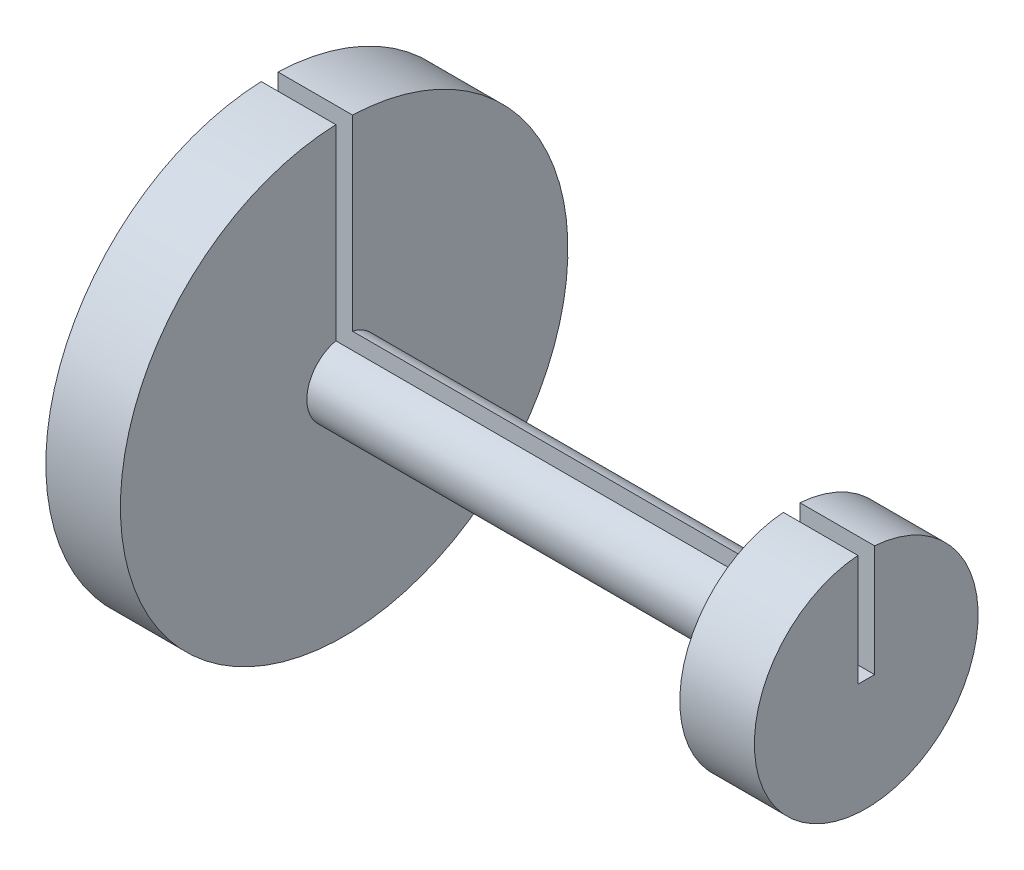
SolidWorks part; units mm, degrees
ref_plane "Front Plane" through (0, 0, 0) normal (0, 0, 1) x (1, 0, 0)
ref_plane "Top Plane" through (0, 0, 0) normal (0, 1, 0) x (1, 0, 0)
ref_plane "Right Plane" through (0, 0, 0) normal (1, 0, 0) x (0, 0, -1)
sketch "Sketch1" plane through (0, 0, 0) normal (0, 0, 1) x (1, 0, 0)
  line L0 (0, 0) -> (0, 30)
  line L1 (0, 30) -> (10, 30)
  line L2 (10, 30) -> (10, 5)
  line L3 (10, 5) -> (70, 5)
  line L4 (70, 5) -> (70, 15)
  line L5 (70, 15) -> (80, 15)
  line L6 (80, 15) -> (80, 0)
  line L7 (80, 0) -> (0, 0) construction
  line L8 (0, 0) -> (80, 0)
  dimension "D1" = 5
  dimension "D2" = 60
  dimension "D3" = 10
  dimension "D4" = 10
  dimension "D5" = 60
  dimension "D6" = 30
revolve "Revolve1" add sketch "Sketch1" angle 360 about L7
sketch "Sketch2" plane through (80, 0, 0) normal (1, 0, 0) x (0, 0, -1)
  line L1 (-1.1166, 0) -> (1.1166, 0)
  line L2 (-1.1166, 0) -> (-1.1166, 31.6073)
  line L3 (-1.1166, 31.6073) -> (1.1166, 31.6073)
  line L4 (1.1166, 0) -> (1.1166, 31.6073)
  point P5 (0, 0)
  dimension "D1" = 31.6073
  dimension "D2" = 2.2331
extrude "Cut-Extrude1" cut sketch "Sketch2" against normal up to vertex (80 mm away) up to point (0, 0, 0)
